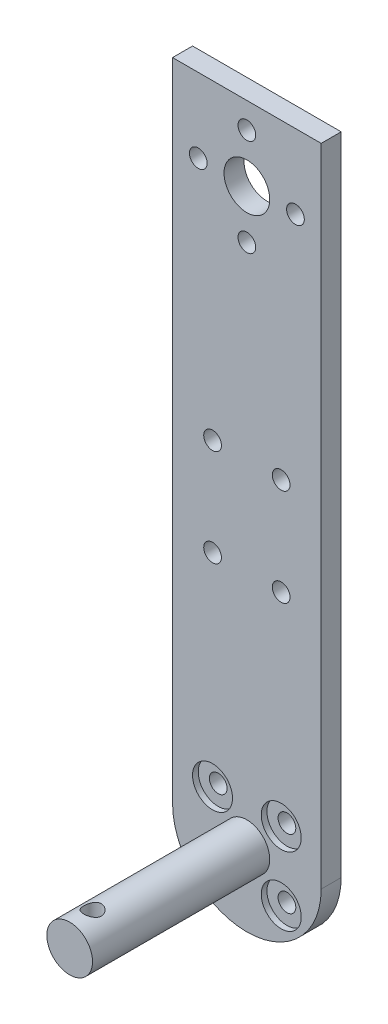
SolidWorks part; units mm, degrees
ref_plane "Front Plane" through (0, 0, 0) normal (0, 0, 1) x (1, 0, 0)
ref_plane "Top Plane" through (0, 0, 0) normal (0, 1, 0) x (1, 0, 0)
ref_plane "Right Plane" through (0, 0, 0) normal (1, 0, 0) x (0, 0, -1)
sketch "Sketch1" plane through (0, 0, 0) normal (0, 0, 1) x (1, 0, 0)
  line L0 (-13, 0) -> (13, 0) construction
  line L1 (13, 0) -> (13, 113)
  line L2 (13, 113) -> (-13, 113)
  line L3 (-13, 0) -> (-13, 113)
  line L4 (0, 0) -> (6.0104, 6.0104) construction
  line L5 (0, 0) -> (0, 100) construction
  line L6 (0, 0) -> (0, 41.5) construction
  line L7 (6, 41.5) -> (-6, 41.5) construction
  line L8 (0, 100) -> (0, 58.5) construction
  line L9 (-6, 58.5) -> (6, 58.5) construction
  arc A1 (13, 0) -> (-13, 0) centre (0, 0) cw
  circle A2 centre (0, 0) radius 8.5 construction
  circle A3 centre (6.0104, 6.0104) radius 1.55
  circle A4 centre (6.0104, -6.0104) radius 1.55
  circle A5 centre (-6.0104, -6.0104) radius 1.55
  circle A6 centre (-6.0104, 6.0104) radius 1.55
  circle A7 centre (0, 0) radius 4 construction
  circle A8 centre (0, 100) radius 4
  circle A9 centre (0, 100) radius 8.5 construction
  circle A10 centre (0, 108.5) radius 1.55
  circle A11 centre (8.5, 100) radius 1.55
  circle A12 centre (0, 91.5) radius 1.55
  circle A13 centre (-8.5, 100) radius 1.55
  circle A14 centre (6, 58.5) radius 1.55
  circle A15 centre (6, 41.5) radius 1.55
  circle A16 centre (-6, 58.5) radius 1.55
  circle A17 centre (-6, 41.5) radius 1.55
  point P6 (0, 0)
  point P19 (0, 0)
  point P31 (0, 100)
  point P33 (0, 41.5)
  point P38 (0, 58.5)
  dimension "D1" = 4
  dimension "D2" = 4
extrude "Boss-Extrude1" add sketch "Sketch1" along normal blind 3.5
sketch "Sketch2" plane through (0, 0, 3.5) normal (0, 0, 1) x (1, 0, 0)
  circle A0 centre (0, 0) radius 4
extrude "Boss-Extrude2" add sketch "Sketch2" along normal blind 31
sketch "Sketch3" plane through (0, 0, 3.5) normal (0, 0, 1) x (1, 0, 0)
  circle A0 centre (-6.0104, 6.0104) radius 3.5
  circle A1 centre (6.0104, 6.0104) radius 3.5
  circle A2 centre (6.0104, -6.0104) radius 3.5
  circle A3 centre (-6.0104, -6.0104) radius 3.5
  point P12 (0, 0)
  dimension "D1" = 4
extrude "Cut-Extrude1" cut sketch "Sketch3" against normal blind 1
ref_axis "Axis1" through (0, 0, 34.5) along (0, 0, -1)
ref_plane "Plane1" through (0, 0, 0) normal (0, -1, 0) x (0, 0, -1)
sketch "Sketch4" plane through (0, 0, 0) normal (0, -1, 0) x (0, 0, -1)
  line L0 (-34.5, 0) -> (-30.5, 0) construction
  line L1 (-34.5, 4) -> (-34.5, -4) construction
  line L2 (-34.5, 0) -> (-3.5, 0) construction
  circle A0 centre (-30.5, 0) radius 1.55
extrude "Cut-Extrude2" cut sketch "Sketch4" against normal up to surface and the other way up to surface up to face at (4, 0, 34.5) other way up to face at (4, 0, 34.5)
